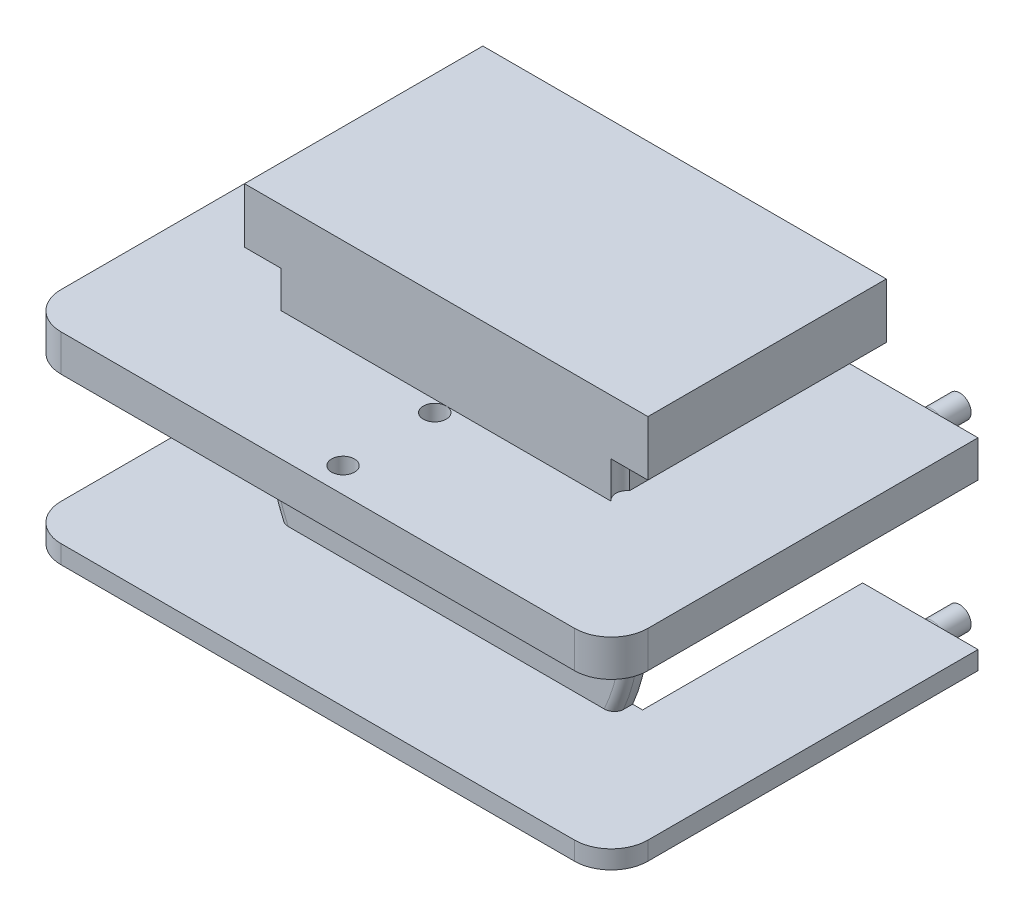
SolidWorks part; units mm, degrees
material "UNOBTANIUM"
ref_plane "Top Plane" through (0, 0, 0) normal (0, 0, 1) x (1, 0, 0)
ref_plane "Right Plane" through (0, 0, 0) normal (0, 1, 0) x (1, 0, 0)
ref_plane "Front Plane" through (0, 0, 0) normal (1, 0, 0) x (0, 0, -1)
ref_axis "x-axis" through (-17.6, 0, 0) along (1, 0, 0)
ref_axis "y-axis" through (0, -9.7375, 0) along (0, 1, 0)
ref_axis "z-axis" through (0, 0, 8.775) along (0, 0, -1)
sketch "Sketch1" plane through (0, 0, 0) normal (0, 0, 1) x (1, 0, 0)
  line L0 (-11, 6) -> (-11, 11)
  line L1 (-11, -6) -> (11, -6)
  line L2 (-11, -6) -> (-11, 6)
  line L3 (-11, 6) -> (11, 6) construction
  line L4 (11, -6) -> (11, 6)
  line L5 (-11, -6) -> (11, 6) construction
  line L6 (-11, 6) -> (11, -6) construction
  line L7 (-11, 11) -> (11, 11)
  line L8 (11, 11) -> (11, 6)
  circle A0 centre (0, 0) radius 9.25 construction
  point P0 (0, 0)
  dimension "D1" = 18.5
  dimension "D2" = 22
  dimension "D3" = 12
  dimension "D4" = 5
extrude "Boss-Extrude1" add sketch "Sketch1" along normal blind 1
sketch "Sketch2" plane through (0, 0, 0) normal (0, 0, -1) x (-1, 0, 0)
  circle A0 centre (0, 0) radius 1.48
  dimension "D1" = 2.96
extrude "Boss-Extrude2" add sketch "Sketch2" along normal blind 14
sketch "Sketch3" plane through (0, 0, 0) normal (0, 0, -1) x (-1, 0, 0)
  line L0 (11, -6) -> (-11, 6) construction
  circle A0 centre (0, 0) radius 1.8
  dimension "D1" = 3.6
extrude "Boss-Extrude3" add sketch "Sketch3" along normal blind 0.85
sketch "Sketch4" plane through (0, 0, 0) normal (0, 0, -1) x (-1, 0, 0)
  line L0 (11, -6) -> (-11, -6) construction
  line L1 (11, 11) -> (9, 11)
  line L2 (11, 11) -> (11, -6)
  line L3 (11, -6) -> (9, -6)
  line L4 (9, 11) -> (9, -6)
  line L5 (0, -6) -> (0, 11) construction
  line L7 (-9, 11) -> (-9, -6)
  line L8 (-11, -6) -> (-9, -6)
  line L9 (-11, 11) -> (-11, -6)
  line L10 (-11, 11) -> (-9, 11)
  line L11 (11, 11) -> (-11, 11) construction
  dimension "D1" = 2
extrude "Boss-Extrude4" add sketch "Sketch4" along normal blind 12
sketch "Sketch5" plane through (0, 0, 0) normal (0, 0, -1) x (-1, 0, 0)
  line L0 (-9, -6) -> (-9, 11) construction
  line L1 (9, 11) -> (-9, 11)
  line L2 (9, 11) -> (9, 9)
  line L3 (9, 9) -> (-9, 9)
  line L4 (-9, 11) -> (-9, 9)
  dimension "D1" = 2
extrude "Boss-Extrude5" add sketch "Sketch5" along normal up to surface (12 mm away) up to face at (-10, 2.5, -12)
sketch "Sketch6" plane through (11, 0, 0) normal (1, 0, 0) x (0, 0, -1)
  line L0 (-1, -6) -> (-1, 11) construction
  line L1 (12, -6) -> (-1, -6)
  line L2 (12, -6) -> (12, -4)
  line L3 (12, -4) -> (-1, -4)
  line L4 (-1, -6) -> (-1, -4)
  line L6 (12, 11) -> (12, -6) construction
  line L7 (-1, 6) -> (12, 6)
  line L8 (-1, 6) -> (-1, 4)
  line L9 (-1, 4) -> (12, 4)
  line L10 (12, 6) -> (12, 4)
  line L11 (5.5, 4) -> (5.5, -4) construction
  line L12 (0, 0) -> (5.5, 0) construction
  line L13 (0, -6) -> (0, 6) construction
  point P21 (5.5, 0)
  dimension "D1" = 2
extrude "Boss-Extrude6" add sketch "Sketch6" along normal blind 5
mirror "Mirror1" about plane through (0, 0, 0) normal (1, 0, 0) of "Boss-Extrude6"
sketch "Sketch7" plane through (0, 0, -12) normal (0, 0, -1) x (-1, 0, 0)
  line L0 (-9, -6) -> (-9, 9) construction
  line L1 (-9, 0) -> (-9, 9)
  line L2 (-9, 9) -> (0, 9)
  line L3 (-9, 0) -> (-9, -6)
  line L4 (-9, -6) -> (-6.7082, -6)
  line L5 (11, -6) -> (-11, -6) construction
  arc A0 (0, 9) -> (-6.7082, -6) centre (0, 0) ccw
  line M18 (-9, -6) -> (-9, 9)
  line M19 (-9, 9) -> (9, 9)
extrude "Boss-Extrude7" add sketch "Sketch7" against normal up to surface (12 mm away) contours A0 L4 M18 | A0 M19 M18 region at (8.3306, -4.5409, -12) region at (6.9897, 6.9897, -12) up to face at (1.8, 0, 0)
sketch "Sketch8" plane through (0, 0, -12) normal (0, 0, -1) x (-1, 0, 0)
  line L0 (-11, 4) -> (-9.1652, 4)
  line L1 (-11, 4) -> (-11, -4)
  line L2 (-11, -4) -> (-9.1652, -4)
  arc A1 (-9.1652, 4) -> (-9.1652, -4) centre (0, 0) ccw
  dimension "D1" = 10
extrude "Cut-Extrude1" cut sketch "Sketch8" against normal through all
sketch "Sketch9" plane through (0, 0, -12) normal (0, 0, -1) x (-1, 0, 0)
  line L0 (-16, -4) -> (-9.1652, -4) construction
  line L1 (-8.0623, 4) -> (-11, 4)
  line L2 (-8.0623, 4) -> (-8.0623, -4)
  line L3 (-8.0623, -4) -> (-11, -4)
  line L4 (-11, 4) -> (-11, -4)
  line L5 (-11, -6) -> (-11, 6) construction
  arc A0 (0, 9) -> (-6.7082, -6) centre (0, 0) ccw construction
  arc A1 (0, 9) -> (-6.7082, -6) centre (0, 0) ccw construction
extrude "Cut-Extrude2" cut sketch "Sketch9" against normal up to surface (12 mm away) up to face at (1.8, 0, 0)
mirror "Mirror2" about plane through (0, 0, 0) normal (1, 0, 0) of "Cut-Extrude2", "Cut-Extrude1", "Boss-Extrude7"
sketch "Sketch21" plane through (0, 0, -12) normal (0, 0, -1) x (-1, 0, 0)
  circle A0 centre (0, 0) radius 10.5
  circle A1 centre (0, 0) radius 9 construction
  circle A2 centre (0, 0) radius 1.8 construction
  circle A3 centre (0, 0) radius 1.8
  dimension "D1" = 1.5
extrude "Cut-Extrude11" cut sketch "Sketch21" against normal up to surface (12 mm away) up to face at (0, -0.7091, 0)
sketch "Sketch10" plane through (0, 0, 1) normal (0, 0, 1) x (1, 0, 0)
  line L0 (-16, -4) -> (-16, -6) construction
  line L1 (16, -6) -> (-16, -6)
  line L2 (16, -6) -> (16, -4)
  line L3 (16, -4) -> (-16, -4)
  line L4 (-16, -6) -> (-16, -4)
  line L5 (-16, -4) -> (-9.1652, -4) construction
  line L7 (-16, 6) -> (16, 6)
  line L8 (-16, 6) -> (-16, 4)
  line L9 (-16, 4) -> (16, 4)
  line L10 (16, 6) -> (16, 4)
extrude "Boss-Extrude8" add sketch "Sketch10" along normal blind 7
fillet "Fillet1" radius 0.5 2 edges at (10, 0, 1) (-10, 0, 1)
sketch "Sketch11" plane through (0, 0, -12) normal (0, 0, -1) x (-1, 0, 0)
  line L0 (-16, -5) -> (-13, -5) construction
  line L1 (-16, -6) -> (-16, -4) construction
  circle A0 centre (-13, -5) radius 0.625
  dimension "D1" = 1.25
  dimension "D2" = 3
extrude "Boss-Extrude9" add sketch "Sketch11" along normal blind 2
sketch "Sketch14" plane through (0, 0, -12) normal (0, 0, -1) x (-1, 0, 0)
  line L1 (11, 6) -> (9, 6)
  line L2 (11, 6) -> (11, 8)
  line L3 (11, 8) -> (9, 8)
  line L4 (9, 6) -> (9, 8)
  line L5 (-11, 6) -> (-9, 6)
  line L6 (-11, 6) -> (-11, 8)
  line L7 (-11, 8) -> (-9, 8)
  line L8 (-9, 6) -> (-9, 8)
  dimension "D1" = 18
  dimension "D2" = 2
extrude "Cut-Extrude5" cut sketch "Sketch14" against normal through all
sketch "Sketch12" plane through (0, 0, -12) normal (0, 0, -1) x (-1, 0, 0)
  line L0 (-16, -5) -> (-13, -5) construction
  line L1 (-16, -6) -> (-16, -4) construction
  line L3 (16, -5) -> (13, -5) construction
  line L4 (16, -6) -> (16, -4) construction
  circle A0 centre (13, -5) radius 0.675
  circle A1 centre (-13, -5) radius 0.625 construction
  circle A2 centre (-13, -5) radius 0.625 construction
  dimension "D1" = 1.35
  dimension "D2" = 1.25
extrude "Cut-Extrude3" cut sketch "Sketch12" against normal blind 2.5
sketch "Sketch16" plane through (0, 6, 0) normal (0, 1, 0) x (1, 0, 0)
  line L0 (-9, -1) -> (-9, 12) construction
  line L1 (-9, 0) -> (-9, -1)
  arc A1 (-9, 0) -> (-9, -1) centre (-9.375, -0.5) cw
  dimension "D1" = 0.25
  dimension "D2" = 1
extrude "Cut-Extrude6" cut sketch "Sketch16" along normal blind 2
mirror "Mirror3" about plane through (0, 0, 0) normal (0, 1, 0) of "Boss-Extrude9", "Cut-Extrude3"
mirror "Mirror4" about plane through (0, 0, 0) normal (1, 0, 0) of "Cut-Extrude6"
fillet "Fillet2" radius 0.5 2 edges at (12.375, 5, -12) (13.625, -5, -12)
fillet "Fillet3" radius 0.5 2 edges at (-13.675, 5, -12) (-13.675, -5, -12)
fillet "Fillet4" radius 2 4 edges at (16, -5, 8) (16, 5, 8) (-16, -5, 8) (-16, 5, 8)
sketch "Sketch17" plane through (0, -6, 0) normal (0, -1, 0) x (1, 0, 0)
  line L0 (-16, 6) -> (-16, -12) construction
  line L1 (-14, 8) -> (14, 8) construction
  line L2 (16, 6) -> (16, -12) construction
  line L3 (-16, 6) -> (-16, -12)
  line L4 (-14, 8) -> (14, 8)
  line L5 (16, 6) -> (16, -12)
  line L6 (14.5, 6) -> (14.5, -12)
  line L8 (-14, 6.5) -> (14, 6.5)
  line L9 (-14.5, 6) -> (-14.5, -12)
  line L10 (14.5, -12) -> (16, -12)
  line L11 (-14.5, -12) -> (-16, -12)
  arc A0 (-14, 8) -> (-16, 6) centre (-14, 6) ccw construction
  arc A1 (16, 6) -> (14, 8) centre (14, 6) ccw construction
  arc A2 (-14, 8) -> (-16, 6) centre (-14, 6) ccw
  arc A3 (16, 6) -> (14, 8) centre (14, 6) ccw
  arc A4 (14.5, 6) -> (14, 6.5) centre (14, 6) ccw
  arc A5 (-14, 6.5) -> (-14.5, 6) centre (-14, 6) ccw
  dimension "D1" = 1.5
extrude "Cut-Extrude7" cut sketch "Sketch17" against normal blind 1 and the other way through all
sketch "Sketch19" plane through (0, 6, 0) normal (0, 1, 0) x (1, 0, 0)
  line L0 (9, -1) -> (-9, -1) construction
  line L1 (0, -1.625) -> (0, -1) construction
  line L2 (9, -1) -> (-9, -1) construction
  circle A0 centre (0, -1.625) radius 0.625
  circle A1 centre (0, -6.625) radius 0.625
  point P4 (0, -1)
  dimension "D1" = 1.25
  dimension "D2" = 5
extrude "Cut-Extrude9" cut sketch "Sketch19" against normal up to surface (2 mm away) up to face at (0.0154, 4, -3.1999)
sketch "Sketch20" plane through (0, 0, -12) normal (0, 0, -1) x (-1, 0, 0)
  line L0 (-9, 8) -> (-11, 8) construction
  line L1 (-11, 11) -> (-9, 11)
  line L2 (-11, 11) -> (-11, 8)
  line L3 (-11, 8) -> (-9, 8)
  line L4 (-9, 11) -> (-9, 8)
  line L5 (11, 11) -> (-11, 11) construction
  line L6 (11, 8) -> (9, 8)
  line L7 (11, 8) -> (11, 11)
  line L8 (11, 11) -> (9, 11)
  line L9 (9, 8) -> (9, 11)
  dimension "D1" = 2
fillet "Fillet5" radius 0.4 1 edges at (-1.48, 0, -14)
equation "\"D1@Sketch12\"=\"D2@Sketch12\"+.1"
